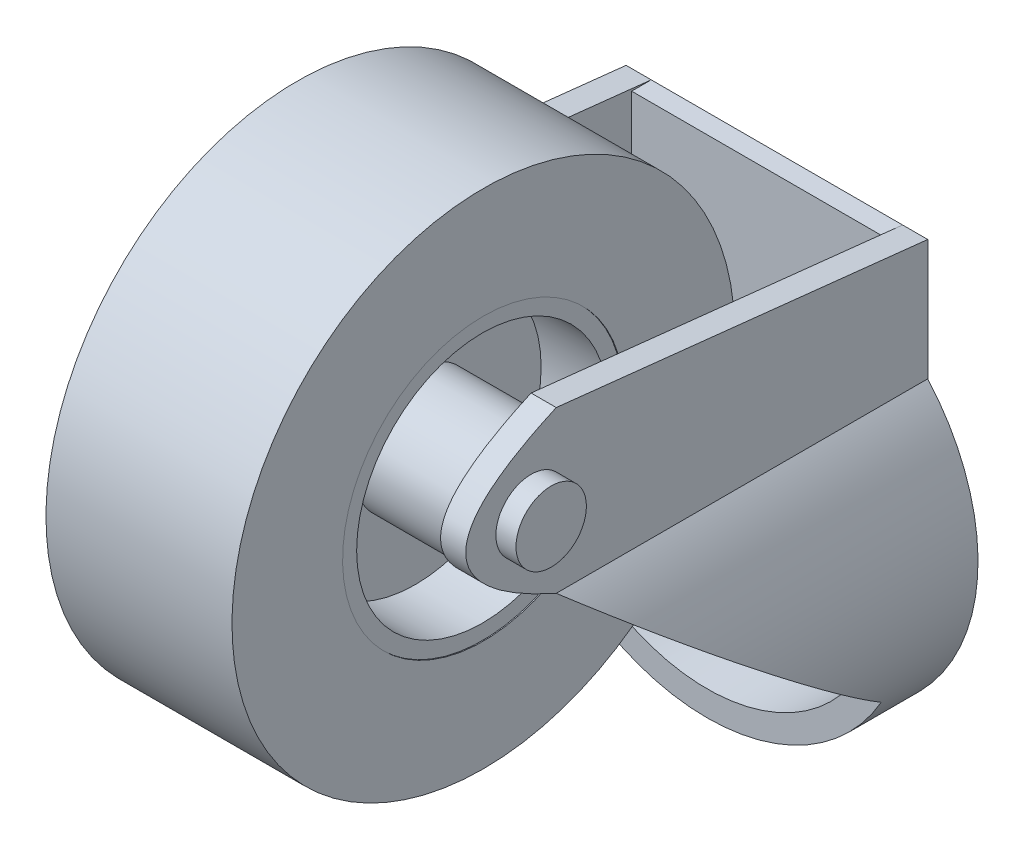
SolidWorks part; units mm, degrees
ref_plane "Front Plane" through (0, 0, 0) normal (0, 0, 1) x (1, 0, 0)
ref_plane "Top Plane" through (0, 0, 0) normal (0, 1, 0) x (1, 0, 0)
ref_plane "Right Plane" through (0, 0, 0) normal (1, 0, 0) x (0, 0, -1)
sketch "Sketch1" plane through (0, 0, 0) normal (0, 0, 1) x (1, 0, 0)
  line L0 (0, 0) -> (0, 7.5) construction
  line L1 (-15, 25.2287) -> (15, 25.2287)
  line L2 (-15, 13.2287) -> (-15, 25.2287)
  line L3 (15, 13.2287) -> (15, 25.2287)
  circle A0 centre (0, 0) radius 7.5
  arc A1 (-15, 13.2287) -> (15, 13.2287) centre (0, 0) ccw
  point P4 (-15, 13.2287)
  point P5 (15, 13.2287)
  dimension "D1" = 20
extrude "Boss-Extrude1" add sketch "Sketch1" along normal blind 1.95 contours A0 | A1 L3 L1 L2
sketch "Sketch4" plane through (0, 0, 1.95) normal (0, 0, 1) x (1, 0, 0)
  line L0 (-12.5, 25.2287) -> (-12.5, 12.2474)
  line L1 (-15, 25.2287) -> (15, 25.2287) construction
  line L2 (-15, 25.2287) -> (-15, 13.2287)
  line L3 (12.5, 25.2287) -> (12.5, 12.2474)
  line L4 (15, 25.2287) -> (15, 13.2287)
  line L5 (-15, 25.2287) -> (-12.5, 25.2287)
  line L6 (12.5, 25.2287) -> (15, 25.2287)
  arc A0 (-15, 13.2287) -> (15, 13.2287) centre (0, 0) ccw
  arc A1 (-12.5, 12.2474) -> (12.5, 12.2474) centre (0, 0) ccw
  point P4 (-15, 25.2287)
  dimension "D2" = 2.5
extrude "Boss-Extrude2" add sketch "Sketch4" along normal blind 5
sketch "Sketch7" plane through (0, 0, 6.95) normal (0, 0, 1) x (1, 0, 0)
  line L1 (-17.3205, -10) -> (-14.3614, -10)
  line L2 (17.3205, -10) -> (14.3614, -10)
  line L3 (-15, 13.2287) -> (-15, 25.2287)
  line L4 (-15, 25.2287) -> (-12.5, 25.2287)
  line L5 (-12.5, 25.2287) -> (-12.5, 15.6125)
  line L6 (-12.5, 12.2474) -> (-12.5, 25.2287) construction
  line L7 (12.5, 25.2287) -> (12.5, 15.6125)
  line L8 (12.5, 25.2287) -> (12.5, 12.2474) construction
  line L9 (12.5, 25.2287) -> (15, 25.2287)
  line L10 (15, 25.2287) -> (15, 13.2287)
  line L11 (-12.5, 15.6125) -> (-12.5, 12.2474)
  line L12 (12.5, 15.6125) -> (12.5, 12.2474)
  arc A0 (-15, 13.2287) -> (15, 13.2287) centre (0, 0) ccw construction
  arc A1 (-12.5, 12.2474) -> (12.5, 12.2474) centre (0, 0) ccw construction
  arc A2 (-12.5, 12.2474) -> (12.5, 12.2474) centre (0, 0) ccw construction
  arc A4 (-15, 13.2287) -> (-17.3205, -10) centre (0, 0) ccw
  arc A5 (-12.5, 12.2474) -> (-14.3614, -10) centre (0, 0) ccw
  arc A6 (14.3614, -10) -> (12.5, 12.2474) centre (0, 0) ccw
  arc A7 (17.3205, -10) -> (15, 13.2287) centre (0, 0) ccw
  point P0 (0, -20)
  point P1 (-17.3205, -10)
  point P8 (17.3205, -10)
extrude "Boss-Extrude3" add sketch "Sketch7" along normal blind 40
sketch "Sketch10" plane through (15, 0, 0) normal (1, 0, 0) x (0, 0, -1)
  line L0 (-46.95, 25.2287) -> (-46.95, 29.2287)
  line L1 (-46.95, 13.2287) -> (0, 13.2287) construction
  line L3 (-46.95, 29.2287) -> (-36.95, 29.2287)
  line L4 (-46.95, 25.2287) -> (-46.95, 13.2287)
  line L5 (-46.95, 13.2287) -> (-36.95, 13.2287)
  spline S0 degree 2 poles (-36.95, 29.2287) (-54.95, 21.2287) (-36.95, 13.2287) knots 0 0 0 1 1 1
  point P0 (-45.95, 21.2287)
  point P1 (-36.95, 13.2287)
  point P7 (-36.95, 13.2287)
  point P9 (-36.95, 13.2287)
  point P10 (-65.9272, 20.8441)
  point P11 (-36.95, 29.2287)
ref_plane "Plane2" through (25, 0, 0) normal (1, 0, 0) x (0, 0, -1)
sketch "Sketch19" plane through (15, 0, 0) normal (1, 0, 0) x (0, 0, -1)
  line L0 (-36.95, 29.2287) -> (0, 25.2287)
  line L1 (0, 25.2287) -> (-36.95, 25.2287)
  line L2 (-46.95, 25.2287) -> (0, 25.2287) construction
  line L3 (-36.95, 25.2287) -> (-36.95, 29.2287)
extrude "Boss-Extrude5" add sketch "Sketch19" against normal blind 2.5
sketch "Sketch20" plane through (15, 0, 0) normal (1, 0, 0) x (0, 0, -1)
  line L0 (-36.95, 25.2287) -> (-36.95, 29.2287)
  line L1 (-36.95, 29.2287) -> (-46.95, 29.2287)
  line L2 (-46.95, 29.2287) -> (-46.95, 25.2287)
  line L3 (-46.95, 25.2287) -> (-36.95, 25.2287)
extrude "Boss-Extrude6" add sketch "Sketch20" against normal blind 2.5
sketch "Sketch22" plane through (-15, 0, 0) normal (-1, 0, 0) x (0, 0, 1)
  line L0 (46.95, 25.2287) -> (46.95, 29.2287)
  line L1 (46.95, 29.2287) -> (36.95, 29.2287)
  line L2 (36.95, 29.2287) -> (0, 25.2287)
  line L3 (0, 25.2287) -> (46.95, 25.2287)
extrude "Boss-Extrude7" add sketch "Sketch22" against normal blind 2.5
extrude "Cut-Extrude8" cut sketch "Sketch10" against normal blind 42.5
sketch "Sketch24" plane through (15, 0, 0) normal (1, 0, 0) x (0, 0, -1)
  line L0 (-36.95, 13.2287) -> (-6.95, -10)
  line L1 (-6.95, -10) -> (-46.95, -10)
  line L2 (-46.95, -10) -> (-46.95, 13.2287)
  line L3 (-46.95, 13.2287) -> (-36.95, 13.2287)
extrude "Cut-Extrude9" cut sketch "Sketch24" against normal blind 42.5 and the other way blind 42.5
sketch "Sketch25" plane through (-15, 0, 0) normal (-1, 0, 0) x (0, 0, 1)
  circle A0 centre (39.45, 21.2287) radius 3.5
  parabola Q0 (36.95, 29.2287) -> (36.95, 13.2287) focus (44.1722, 21.2287) apex (45.95, 21.2287) construction
  point P0 (39.45, 21.2287)
  point P1 (39.45, 21.2287)
  point P2 (45.95, 21.2287)
  dimension "D1" = 6.5
extrude "Boss-Extrude8" add sketch "Sketch25" along normal blind 2
sketch "Sketch26" plane through (15, 0, 0) normal (1, 0, 0) x (0, 0, -1)
  circle A0 centre (-39.45, 21.2287) radius 3.5
  parabola Q0 (-36.95, 13.2287) -> (-36.95, 29.2287) focus (-44.1722, 21.2287) apex (-45.95, 21.2287) construction
  point P0 (-45.95, 21.2287)
  point P1 (-39.45, 21.2287)
  dimension "D1" = 6.5
extrude "Boss-Extrude9" add sketch "Sketch26" along normal blind 2
sketch "Sketch27" plane through (12.5, 0, 0) normal (-1, 0, 0) x (0, 0, 1)
  circle A0 centre (38.7, 21.2287) radius 6
  parabola Q0 (36.95, 13.2287) -> (36.95, 29.2287) focus (44.1722, 21.2287) apex (45.95, 21.2287) construction
  point P0 (45.95, 21.2287)
  point P1 (38.7, 21.2287)
  dimension "D1" = 7.25
extrude "Boss-Extrude10" add sketch "Sketch27" along normal blind 12.25
sketch "Sketch33" plane through (0.25, 0, 0) normal (-1, 0, 0) x (0, 0, 1)
  circle A0 centre (38.7, 21.2287) radius 12.5
  circle A1 centre (38.7, 21.2287) radius 25
  point P0 (38.7, 21.2287)
extrude "Boss-Extrude11" add sketch "Sketch33" along normal mid plane 18.5 separate body
sketch "Sketch40" plane through (0.25, 0, 0) normal (-1, 0, 0) x (0, 0, 1)
  circle A0 centre (38.7, 21.2287) radius 12.5
  point P0 (38.7, 21.2287)
extrude "Boss-Extrude13" add sketch "Sketch40" along normal mid plane 5
sketch "Sketch34" plane through (-12.5, 0, 0) normal (1, 0, 0) x (0, 0, -1)
  circle A0 centre (-38.7, 21.2287) radius 6
  parabola Q0 (-36.95, 29.2287) -> (-36.95, 13.2287) focus (-44.1722, 21.2287) apex (-45.95, 21.2287) construction
  point P0 (-45.95, 21.2287)
  point P1 (-38.7, 21.2287)
  dimension "D1" = 7.25
extrude "Boss-Extrude12" add sketch "Sketch34" along normal up to next
sketch "Sketch47" plane through (-9, 0, 0) normal (-1, 0, 0) x (0, 0, 1)
  circle A0 centre (38.7, 21.2287) radius 14
  circle A1 centre (38.7, 21.2287) radius 12.5
extrude "Cut-Extrude10" cut sketch "Sketch47" against normal blind 0.1
sketch "Sketch48" plane through (9.5, 0, 0) normal (1, 0, 0) x (0, 0, -1)
  circle A0 centre (-38.7, 21.2287) radius 14
  circle A1 centre (-38.7, 21.2287) radius 12.5
extrude "Cut-Extrude13" cut sketch "Sketch48" against normal blind 0.1
